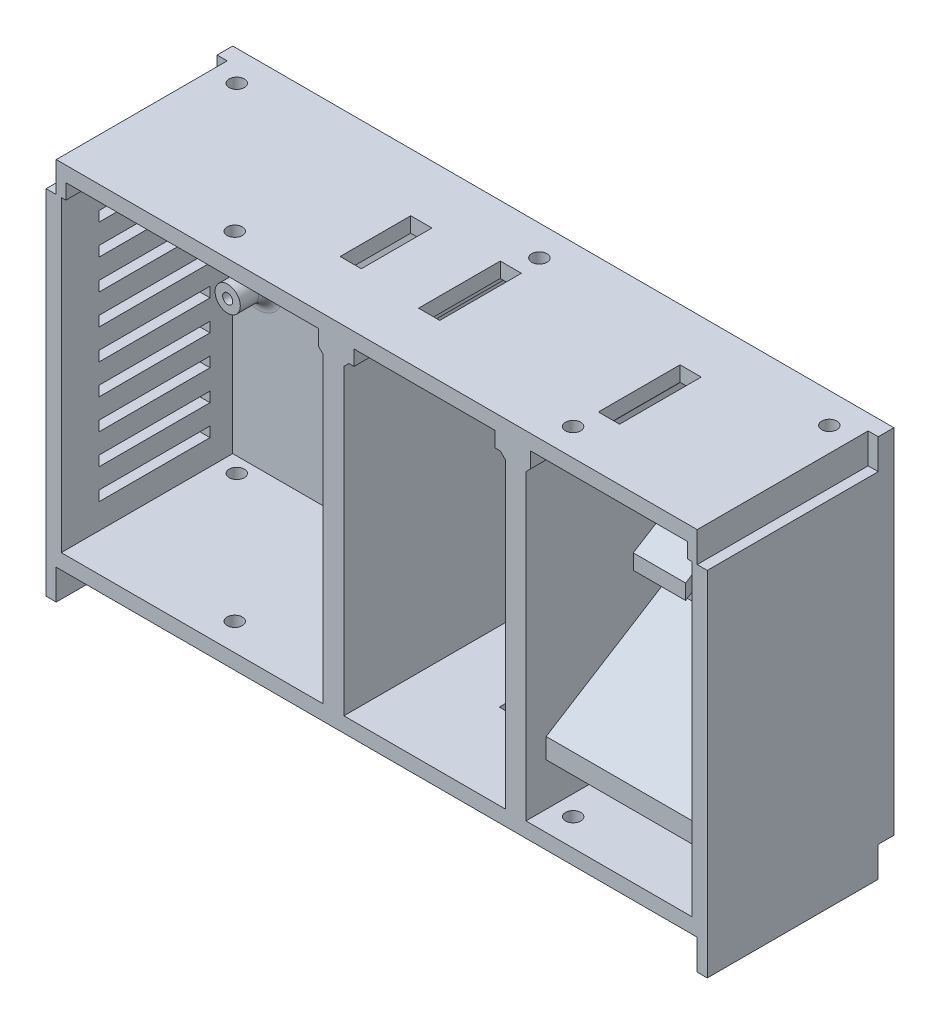
SolidWorks part; units mm, degrees
material "ABS"
ref_plane "Alzado" through (0, 0, 0) normal (0, 0, 1) x (1, 0, 0)
ref_plane "Planta" through (0, 0, 0) normal (0, 1, 0) x (1, 0, 0)
ref_plane "Vista lateral" through (0, 0, 0) normal (1, 0, 0) x (0, 0, -1)
sketch "Croquis1" plane through (0, 0, 0) normal (0, 0, 1) x (1, 0, 0)
  line L0 (0, 0) -> (2, 0)
  line L1 (2, 0) -> (2, 6)
  line L2 (55, 0) -> (55, 6)
  line L3 (55, 6) -> (2, 6)
  line L4 (56, 0) -> (56, 6)
  line L5 (56, 6) -> (58, 6)
  line L6 (58, 6) -> (58, 0)
  line L7 (58, 0) -> (59, 0)
  line L8 (59, 0) -> (59, 6)
  line L9 (91.1, 0) -> (91.1, 6)
  line L10 (59, 6) -> (91.1, 6)
  line L11 (92.1, 0) -> (92.1, 6)
  line L12 (92.1, 6) -> (94.1, 6)
  line L13 (94.1, 6) -> (94.1, 0)
  line L14 (95.1, 0) -> (95.1, 6)
  line L15 (129.1, 0) -> (129.1, 6)
  line L16 (129.1, 6) -> (95.1, 6)
  line L17 (0, 0) -> (0, -64)
  line L18 (0, -64) -> (131.1, -64)
  line L19 (131.1, -64) -> (131.1, 0)
  line L20 (55, 0) -> (56, 0)
  line L21 (58, 0) -> (59, 0)
  line L22 (129.1, 0) -> (131.1, 0)
  line L23 (94.1, 0) -> (95.1, 0)
  line L24 (91.1, 0) -> (92.1, 0)
  line L25 (2, 0) -> (129.1, 0)
  line L26 (55, 6) -> (56, 6)
  line L27 (58, 6) -> (59, 6)
  line L28 (91.1, 6) -> (92.1, 6)
  line L29 (94.1, 6) -> (95.1, 6)
  point P3 (2, 0)
  point P4 (129.1, 0)
  point P5 (55, 0)
  point P10 (56, 0)
  point P11 (58, 0)
  point P12 (59, 0)
  point P15 (91.1, 0)
  point P22 (92.1, 0)
  point P23 (94.1, 0)
  point P24 (95.1, 0)
  dimension "D1" = 131.1
  dimension "D2" = 2
  dimension "D3" = 2
  dimension "D4" = 55
  dimension "D5" = 6
  dimension "D6" = 1
  dimension "D7" = 2
  dimension "D8" = 1
  dimension "D9" = 32.1
  dimension "D10" = 1
  dimension "D11" = 2
  dimension "D12" = 1
  dimension "D13" = 64
extrude "Saliente-Extruir1" add sketch "Croquis1" along normal blind 34 contours L8 L25 L9 L10 | L1 L25 L2 L3 | L14 L25 L15 L16 | L11 L25 L13 L12 | L4 L25 L6 L5 | L26 L2 L20 L4 | L27 L6 L7 L8 | L29 L13 L23 L14 | L28 L9 L24 L11 region at (28.5, 3, 0) region at (55.5, 3, 0) region at (57, 3, 0) region at (58.5, 3, 0) region at (112.1, 3, 0) region at (75.05, 3, 0) region at (94.6, 3, 0) region at (91.6, 3, 0) region at (93.1, 3, 0)
sketch "Croquis2" plane through (0, 0, 0) normal (0, 0, 1) x (1, 0, 0)
  line L1 (2, -64) -> (129.1, -64)
  line L3 (129.1, 0) -> (2, 0)
  line L5 (129.1, 0) -> (131.1, 0)
  line L7 (129.1, -64) -> (131.1, -64)
  line L8 (131.1, 0) -> (131.1, -64)
  line L9 (2, -64) -> (0, -64)
  line L11 (2, 0) -> (0, 0)
  line L12 (0, -64) -> (0, 0)
  dimension "D1" = 64
  dimension "D2" = 2
  dimension "D3" = 2
extrude "Saliente-Extruir2" add sketch "Croquis2" along normal blind 3
sketch "Croquis3" plane through (0, 0, 3) normal (0, 0, 1) x (1, 0, 0)
  line L0 (0, -64) -> (131.1, -64) construction
  line L1 (131.1, 0) -> (128.1, 0)
  line L2 (131.1, 0) -> (131.1, -64)
  line L3 (131.1, -64) -> (128.1, -64)
  line L4 (128.1, 0) -> (128.1, -61)
  line L6 (0, 0) -> (3, 0)
  line L7 (0, 0) -> (0, -64)
  line L8 (0, -64) -> (3, -64)
  line L9 (3, 0) -> (3, -61)
  line L10 (3, -64) -> (128.1, -64)
  line L12 (3, -61) -> (128.1, -61)
  dimension "D1" = 3
  dimension "D2" = 3
  dimension "D3" = 3
extrude "Saliente-Extruir3" add sketch "Croquis3" along normal up to vertex (31 mm away) up to point (129.1, 0, 34)
sketch "Croquis4" plane through (0, 0, 0) normal (0, 0, -1) x (-1, 0, 0)
  line L25 (-2, 6) -> (-129.1, 6)
  line L34 (-129.1, 6) -> (-129.1, 0)
  line L35 (-129.1, 0) -> (-131.1, 0)
  line L36 (-131.1, 0) -> (-131.1, -64)
  line L37 (-131.1, -64) -> (0, -64)
  line L38 (0, -64) -> (0, 0)
  line L39 (0, 0) -> (-2, 0)
  line L40 (-2, 0) -> (-2, 6)
  line L49 (-2, 6) -> (-129.1, 6)
  line L58 (-129.1, 6) -> (-129.1, 0)
  line L59 (-129.1, 0) -> (-131.1, 0)
  line L60 (-131.1, 0) -> (-131.1, -64)
  line L61 (-131.1, -64) -> (0, -64)
  line L62 (0, -64) -> (0, 0)
  line L63 (0, 0) -> (-2, 0)
  line L64 (-2, 0) -> (-2, 6)
  dimension "D1" = 0
extrude "Saliente-Extruir4" add sketch "Croquis4" along normal blind 3
sketch "Croquis5" plane through (0, 0, 3) normal (0, 0, 1) x (1, 0, 0)
  line L1 (128.1, -61) -> (3, -61) construction
  line L4 (0, -64) -> (0, 0) construction
  line L23 (54.95, 0.05) -> (59.05, 0.05)
  line L26 (128.1, 0) -> (3, 0) construction
  line L27 (54.95, 0.05) -> (54.95, -61)
  line L28 (59.05, 0.05) -> (59.05, -61)
  line L29 (91.05, 0.05) -> (95.15, 0.05)
  line L32 (196.65, 0) -> (-65.55, 0) construction
  line L33 (91.05, 0.05) -> (91.05, -61)
  line L34 (128.1, -61) -> (3, -61) construction
  line L35 (91.05, -61) -> (95.15, -61)
  line L36 (95.15, -61) -> (95.15, 0.05)
  line M6 (128.1, 0) -> (3, 0)
  line M8 (128.1, 0) -> (3, 0)
  line M10 (128.1, 0) -> (3, 0)
  line M12 (128.1, 0) -> (3, 0)
  line M14 (128.1, 0) -> (3, 0)
  line M16 (3, -61) -> (128.1, -61)
  dimension "D1" = 54.95
  dimension "D2" = 32
  dimension "D3" = 4.1
  dimension "D4" = 0.05
  dimension "D6" = 0.05
extrude "Saliente-Extruir10" add sketch "Croquis5" along normal up to vertex (31 mm away) contours L28 L27 M10 M12 M14 M16 | L36 L33 M16 M6 M8 M10 region at (57, -30.5, 3) region at (93.1, -30.5, 3) up to point (3, 0, 34)
sketch "Croquis6" plane through (0, 0, 0) normal (0, -1, 0) x (1, 0, 0)
  line L0 (0, 34) -> (0, -3) construction
  line L1 (0, 15.5) -> (131.1, 15.5) construction
  line L2 (131.1, 34) -> (131.1, -3) construction
  line L3 (51, 8.5) -> (51, 22.5)
  line L4 (51, 22.5) -> (46.8, 22.5)
  line L5 (46.8, 22.5) -> (46.8, 8.5)
  line L6 (46.8, 8.5) -> (51, 8.5)
  line L7 (99.1, 7.4) -> (99.1, 23.6)
  line L8 (99.1, 23.6) -> (103.3, 23.6)
  line L9 (103.3, 23.6) -> (103.3, 7.4)
  line L10 (103.3, 7.4) -> (99.1, 7.4)
  line L11 (63.45, 7.4) -> (63.45, 23.6)
  line L12 (63.45, 23.6) -> (67.65, 23.6)
  line L13 (67.65, 23.6) -> (67.65, 7.4)
  line L14 (67.65, 7.4) -> (63.45, 7.4)
  point P6 (99.1, 15.5)
  point P9 (51, 15.5)
  point P15 (99.1, 15.5)
  point P17 (63.45, 15.5)
  point P21 (63.45, 15.5)
  dimension "D1" = 51
  dimension "D2" = 4.2
  dimension "D3" = 14
  dimension "D4" = 32
  dimension "D5" = 16.2
  dimension "D6" = 4.2
  dimension "D7" = 12.45
extrude "Cortar-Extruir1" cut sketch "Croquis6" against normal up to next
sketch "Croquis7" plane through (0, 0, 34) normal (0, 0, 1) x (1, 0, 0)
  line L0 (3, 0) -> (54.95, 0) construction
  line L1 (28.975, 0) -> (28.975, 3)
  line L2 (3.925, 3) -> (54.025, 3)
  line L3 (54.025, 3) -> (54.025, 0)
  line L4 (3.925, 0) -> (54.025, 0)
  line L5 (3.925, 3) -> (3.925, 0)
  line L6 (75.05, 0) -> (75.05, 3)
  line L7 (59.05, 0) -> (91.05, 0) construction
  line L8 (75.05, 3) -> (89.05, 3)
  line L9 (89.05, 3) -> (89.05, 0)
  line L10 (89.05, 0) -> (75.05, 0)
  line L11 (75.05, 3) -> (61.05, 3)
  line L12 (61.05, 3) -> (61.05, 0)
  line L13 (61.05, 0) -> (75.05, 0)
  line L14 (61.05, 3) -> (75.05, 3)
  line L15 (111.625, 0) -> (111.625, 3)
  line L16 (95.15, 0) -> (128.1, 0) construction
  line L17 (111.625, 3) -> (127.225, 3)
  line L18 (127.225, 3) -> (127.225, 0)
  line L19 (127.225, 0) -> (111.625, 0)
  line L20 (111.625, 0) -> (96.025, 0)
  line L21 (96.025, 0) -> (96.025, 3)
  line L22 (96.025, 3) -> (111.625, 3)
  line M5 (59.05, 0) -> (91.05, 0)
  line M10 (95.15, 0) -> (128.1, 0)
  line M37 (3, 0) -> (54.95, 0)
  dimension "D1" = 25.05
  dimension "D2" = 3
  dimension "D3" = 14
  dimension "D4" = 15.6
extrude "Cortar-Extruir2" cut sketch "Croquis7" against normal up to vertex (31 mm away) contours L3 L2 L1 M37 | L2 L5 L1 M37 | L11 L12 L6 M5 | L9 L8 L6 M5 | L22 L21 L15 M10 | L18 L17 L15 M10 region at (16.45, 1.5, 34) region at (41.5, 1.5, 34) region at (68.05, 1.5, 34) region at (82.05, 1.5, 34) region at (103.825, 1.5, 34) region at (119.425, 1.5, 34) up to point (54.95, 0, 3)
sketch "Croquis22" plane through (0, 0, 3) normal (0, 0, 1) x (1, 0, 0)
  line L0 (95.15, 0) -> (95.15, -61) construction
  line L1 (95.15, -61) -> (128.1, -61) construction
  line L2 (128.1, -61) -> (128.1, 0) construction
  line L3 (128.1, 0) -> (127.225, 0) construction
  line L4 (127.225, 0) -> (127.225, 3) construction
  line L5 (127.225, 3) -> (96.025, 3) construction
  line L6 (96.025, 3) -> (96.025, 0) construction
  line L7 (96.025, 0) -> (95.15, 0) construction
  line L8 (91.05, -61) -> (91.05, 0) construction
  line L9 (91.05, 0) -> (89.05, 0) construction
  line L10 (89.05, 0) -> (89.05, 3) construction
  line L11 (89.05, 3) -> (61.05, 3) construction
  line L12 (61.05, 3) -> (61.05, 0) construction
  line L13 (61.05, 0) -> (59.05, 0) construction
  line L14 (59.05, 0) -> (59.05, -61) construction
  line L15 (59.05, -61) -> (91.05, -61) construction
  line L16 (54.95, -61) -> (54.95, 0) construction
  line L17 (54.95, 0) -> (54.025, 0) construction
  line L18 (54.025, 0) -> (54.025, 3) construction
  line L19 (54.025, 3) -> (3.925, 3) construction
  line L20 (3.925, 3) -> (3.925, 0) construction
  line L21 (3.925, 0) -> (3, 0) construction
  line L22 (3, 0) -> (3, -61) construction
  line L23 (3, -61) -> (54.95, -61) construction
  line L24 (95.15, 0) -> (95.15, -61)
  line L25 (95.15, -61) -> (128.1, -61)
  line L26 (128.1, -61) -> (128.1, 0)
  line L27 (128.1, 0) -> (127.225, 0)
  line L28 (127.225, 0) -> (127.225, 3)
  line L29 (127.225, 3) -> (96.025, 3)
  line L30 (96.025, 3) -> (96.025, 0)
  line L31 (96.025, 0) -> (95.15, 0)
  line L32 (91.05, -61) -> (91.05, 0)
  line L33 (91.05, 0) -> (89.05, 0)
  line L34 (89.05, 0) -> (89.05, 3)
  line L35 (89.05, 3) -> (61.05, 3)
  line L36 (61.05, 3) -> (61.05, 0)
  line L37 (61.05, 0) -> (59.05, 0)
  line L38 (59.05, 0) -> (59.05, -61)
  line L39 (59.05, -61) -> (91.05, -61)
  line L40 (54.95, -61) -> (54.95, 0)
  line L41 (54.95, 0) -> (54.025, 0)
  line L42 (54.025, 0) -> (54.025, 3)
  line L43 (54.025, 3) -> (3.925, 3)
  line L44 (3.925, 3) -> (3.925, 0)
  line L45 (3.925, 0) -> (3, 0)
  line L46 (3, 0) -> (3, -61)
  line L47 (3, -61) -> (54.95, -61)
extrude "Cortar-Extruir8" cut sketch "Croquis22" against normal blind 3 contours L40 L41 L42 L43 L44 L45 L46 L47 | L32 L33 L34 L35 L36 L37 L38 L39 | L24 L25 L26 L27 L28 L29 L30 L31
sketch "Croquis24" plane through (2, 0, 0) normal (-1, 0, 0) x (0, 0, 1)
  line L0 (34, 0) -> (-3, 0) construction
  line L5 (0.1, 0) -> (-4.3164, 0)
  line L6 (0.1, 0) -> (0.1, 6.5451)
  line L7 (0.1, 6.5451) -> (-4.3164, 6.5451)
  line L8 (-4.3164, 0) -> (-4.3164, 6.5451)
  line L9 (0, 0) -> (0, 8.0802) construction
  dimension "D1" = 0.1
extrude "Cortar-Extruir11" cut sketch "Croquis24" against normal through all contours L6 L5 L8 L7
sketch "Croquis26" plane through (0, 0, 0) normal (0, 0, 1) x (1, 0, 0)
  line L0 (4, -60) -> (54.1, -60)
  line L1 (4, -60) -> (4, -4.1)
  line L2 (4, -4.1) -> (54.1, -4.1)
  line L3 (54.1, -60) -> (54.1, -4.1)
  line L4 (4, -60) -> (54.1, -4.1) construction
  line L5 (4, -4.1) -> (54.1, -60) construction
  line L6 (36.1, -45) -> (46.1, -45)
  line L7 (36.1, -45) -> (36.1, -39)
  line L8 (36.1, -39) -> (46.1, -39)
  line L9 (46.1, -45) -> (46.1, -39)
  line L10 (3, -61) -> (54.95, -61) construction
  line L11 (3, 0) -> (3, -61) construction
  line L12 (54.95, -61) -> (54.95, 0) construction
  circle A0 centre (24, -8.1) radius 1
  circle A1 centre (8, -28.9) radius 1
  circle A2 centre (24, -8.1) radius 2.5
  circle A3 centre (8, -28.9) radius 2.5
  point P0 (29.05, -32.05)
  point P5 (24, -8.1)
  point P8 (8, -28.9)
  dimension "D6" = 2
  dimension "D7" = 5
  dimension "D1" = 1
  dimension "D2" = 55.9
  dimension "D3" = 1
  dimension "D4" = 4
  dimension "D5" = 24.8
  dimension "D8" = 4
  dimension "D9" = 20
  dimension "D10" = 8
  dimension "D11" = 15
  dimension "D12" = 6
  dimension "D13" = 10
  dimension "D14" = 0.85
extrude "Saliente-Extruir16" add sketch "Croquis26" along normal blind 6 contours L6 L9 L8 L7 | A2 A0 | A3 A1 region at (41.1, -42, 0) region at (21.5707, -8.1, 0) region at (5.5707, -28.9, 0)
fillet "Redondeo1" radius 2.4 3 edges at (10.5, -28.9, 0) (26.5, -8.1, 0) (46.1, -42, 0)
chamfer "Chaflán1" distance 1 angle 45 4 edges at (54.95, 0, 17.05) (95.15, 0, 17.05) (91.05, 0, 17.05) (59.05, 0, 17.05)
sketch "Croquis10" plane through (0, 0, 0) normal (-1, 0, 0) x (0, 0, 1)
  line L0 (15.5, -64) -> (15.5, 6) construction
  line L1 (34, -64) -> (-3, -64) construction
  line L3 (4.5, -50) -> (4.5, -48)
  line L4 (4.5, -56) -> (26.5, -56)
  line L5 (4.5, -56) -> (4.5, -54)
  line L6 (4.5, -54) -> (26.5, -54)
  line L7 (26.5, -56) -> (26.5, -54)
  line L8 (4.5, -56) -> (26.5, -54) construction
  line L9 (4.5, -54) -> (26.5, -56) construction
  line L10 (4.5, -50) -> (26.5, -50)
  line L11 (26.5, -50) -> (26.5, -48)
  line L12 (4.5, -48) -> (26.5, -48)
  line L13 (4.5, -44) -> (4.5, -42)
  line L14 (4.5, -44) -> (26.5, -44)
  line L15 (26.5, -44) -> (26.5, -42)
  line L16 (4.5, -42) -> (26.5, -42)
  line L17 (4.5, -38) -> (4.5, -36)
  line L18 (4.5, -38) -> (26.5, -38)
  line L19 (26.5, -38) -> (26.5, -36)
  line L20 (4.5, -36) -> (26.5, -36)
  line L21 (4.5, -32) -> (4.5, -30)
  line L22 (4.5, -32) -> (26.5, -32)
  line L23 (26.5, -32) -> (26.5, -30)
  line L24 (4.5, -30) -> (26.5, -30)
  line L25 (4.5, -26) -> (4.5, -24)
  line L26 (4.5, -26) -> (26.5, -26)
  line L27 (26.5, -26) -> (26.5, -24)
  line L28 (4.5, -24) -> (26.5, -24)
  line L29 (4.5, -20) -> (4.5, -18)
  line L30 (4.5, -20) -> (26.5, -20)
  line L31 (26.5, -20) -> (26.5, -18)
  line L32 (4.5, -18) -> (26.5, -18)
  line L33 (4.5, -14) -> (4.5, -12)
  line L34 (4.5, -14) -> (26.5, -14)
  line L35 (26.5, -14) -> (26.5, -12)
  line L36 (4.5, -12) -> (26.5, -12)
  line L37 (4.5, -8) -> (4.5, -6)
  line L38 (4.5, -8) -> (26.5, -8)
  line L39 (26.5, -8) -> (26.5, -6)
  line L40 (4.5, -6) -> (26.5, -6)
  point P6 (15.5, -55)
  dimension "D1" = 22
  dimension "D2" = 2
  dimension "D3" = 8
  dimension "D4" = 9
extrude "Cortar-Extruir3" cut sketch "Croquis10" against normal up to vertex (3 mm away) contours L4 L7 L6 L5 | L12 L3 L10 L11 | L16 L13 L14 L15 | L20 L17 L18 L19 | L24 L21 L22 L23 | L28 L25 L26 L27 | L32 L29 L30 L31 | L36 L33 L34 L35 | L40 L37 L38 L39 region at (0, -49, 15.5) region at (0, -55, 15.5) region at (0, -43, 15.5) region at (0, -37, 15.5) region at (0, -31, 15.5) region at (0, -25, 15.5) region at (0, -19, 15.5) region at (0, -13, 15.5) region at (0, -7, 15.5) up to point (3, -61, 34)
sketch "Croquis12" plane through (95.15, 0, 0) normal (1, 0, 0) x (0, 0, -1)
  line L0 (0, -29.7544) -> (-34, -51)
  line L1 (0, 0) -> (0, -61) construction
  line L2 (-34, -61) -> (-34, -1) construction
  line L4 (-34, -51) -> (-34, -55)
  line L5 (-34, -55) -> (0, -33.7544)
  line L6 (0, -29.7544) -> (0, -33.7544)
  dimension "D1" = 4
  dimension "D2" = 58
  dimension "D3" = 6
extrude "Saliente-Extruir12" add sketch "Croquis12" along normal up to surface (32.95 mm away) up to face at (128.1, -24.4, 13.62)
sketch "Croquis13" plane through (95.15, 0, 0) normal (1, 0, 0) x (0, 0, -1)
  line L0 (0, -29.7544) -> (0, -20.6544) construction
  line L2 (0, -20.6544) -> (-12.7207, -28.6032)
  line L4 (0, -29.7544) -> (-34, -51) construction
  line L6 (-12.7207, -25.6032) -> (0, -17.6544)
  line L7 (0, -17.6544) -> (0, -20.6544)
  line L8 (-12.7207, -28.6032) -> (-12.7207, -25.6032)
  line L9 (-34, -51) -> (-8.7351, -35.2127) construction
  line L10 (0, -29.7544) -> (-34, -51) construction
  line L11 (-6.7844, -33.9938) -> (-6.7844, -24.8938)
  line L12 (-6.7844, -33.9938) -> (0, -29.7544)
  line L13 (0, 0) -> (0, -29.7544) construction
  line M8 (-34, -51) -> (0, -29.7544)
  line M18 (0, -29.7544) -> (0, 0)
  dimension "D1" = 9.1
  dimension "D2" = 3
  dimension "D3" = 15
  dimension "D4" = 8
extrude "Saliente-Extruir17" add sketch "Croquis13" along normal up to surface (32.95 mm away) contours L11 L2 M8 M18 | L8 L2 L6 M18 region at (95.15, -27.3241, 3.3922) region at (95.15, -23.1288, 6.3604) up to face at (128.1, -52.6886, 17)
ref_plane "Plano1" through (0, -17.6544, 0) normal (0, -1, 0) x (-1, 0, 0)
sketch "Croquis38" plane through (0, -17.6544, 0) normal (0, -1, 0) x (-1, 0, 0)
  line L0 (-111.625, 0) -> (-111.625, -34.0311) construction
  line L1 (-128.1, 0) -> (-95.15, 0) construction
  line L2 (-111.625, 0) -> (-117.725, 0)
  line L3 (-117.725, 0) -> (-117.725, -26)
  line L4 (-117.725, -26) -> (-105.525, -26)
  line L5 (-111.625, 0) -> (-105.525, 0)
  line L6 (-105.525, 0) -> (-105.525, -26)
  dimension "D1" = 6.1
  dimension "D2" = 6.1
  dimension "D3" = 26
  dimension "D4" = 26
extrude "Cortar-Extruir12" cut sketch "Croquis38" along normal up to vertex (16.3394 mm away) contours L0 L2 L3 L4 | L5 L0 L4 L6 region at (108.575, -17.6544, 13) region at (114.675, -17.6544, 13) up to point (128.1, -33.9938, 6.7844)
sketch "Croquis40" plane through (0, 3, 0) normal (0, -1, 0) x (1, 0, 0)
  line L0 (0, 34) -> (0, -3) construction
  line L1 (3.925, 34) -> (54.025, 34) construction
  line L2 (131.1, 34) -> (131.1, -3) construction
  line L3 (0, -3) -> (131.1, -3) construction
  circle A0 centre (32, 28.6) radius 1.5
  circle A1 centre (99.1, 28.6) radius 1.5
  circle A2 centre (6.8, 3) radius 1.5
  circle A3 centre (124.3, 3) radius 1.5
  circle A4 centre (66.8, 3) radius 1.5
  dimension "D3" = 3
  dimension "D1" = 32
  dimension "D2" = 5.4
  dimension "D4" = 32
  dimension "D5" = 6.8
  dimension "D6" = 6
  dimension "D7" = 6.8
  dimension "D8" = 60
extrude "Cortar-Extruir13" cut sketch "Croquis40" against normal up to next
sketch "Croquis48" plane through (0, 0, 0) normal (-1, 0, 0) x (0, 0, 1)
  line L1 (-3, 0) -> (0.1, 0)
  line L2 (-3, 0) -> (-3, 6)
  line L3 (-3, 6) -> (0.1, 6)
  line L4 (0.1, 0) -> (0.1, 6)
extrude "Saliente-Extruir20" add sketch "Croquis48" against normal up to vertex (131.1 mm away) up to point (131.1, 0, -3)
sketch "Croquis49" plane through (0, 0, 34) normal (0, 0, 1) x (1, 0, 0)
  line L0 (2, 0) -> (2, -64) construction
  line L1 (0, -64) -> (131.1, -64) construction
  line L2 (129.1, 0) -> (129.1, -64) construction
  line L4 (2, -64) -> (0, -64)
  line L5 (0, -64) -> (0, -70)
  line L6 (0, -70) -> (2, -70)
  line L7 (2, -70) -> (2, -64)
  line L8 (129.1, -64) -> (131.1, -64)
  line L9 (131.1, -64) -> (131.1, -70)
  line L10 (131.1, -70) -> (129.1, -70)
  line L11 (129.1, -70) -> (129.1, -64)
  line L12 (65.55, -64) -> (68.55, -64)
  line L16 (62.55, -64) -> (65.55, -64)
  dimension "D1" = 6
  dimension "D2" = 3
extrude "Saliente-Extruir21" add sketch "Croquis49" against normal up to vertex (33.9 mm away) contours L6 L7 L4 L5 | L16 | L12 | L11 L10 L9 L8 region at (1, -67, 34) region at (130.1, -67, 34) up to point (2, 0, 0.1)
sketch "Croquis50" plane through (0, -64, 0) normal (0, -1, 0) x (1, 0, 0)
  circle A0 centre (124.3, 3) radius 1.5 construction
  circle A1 centre (99.1, 28.6) radius 1.5 construction
  circle A3 centre (6.8, 3) radius 1.5 construction
  circle A4 centre (32, 28.6) radius 1.5 construction
  circle A5 centre (124.3, 3) radius 1.5
  circle A6 centre (99.1, 28.6) radius 1.5
  circle A8 centre (6.8, 3) radius 1.5
  circle A9 centre (32, 28.6) radius 1.5
extrude "Cortar-Extruir14" cut sketch "Croquis50" against normal up to surface (3 mm away) up to face at (28.975, -61, 17)
sketch "Croquis51" plane through (0, 0, 0) normal (-1, 0, 0) x (0, 0, 1)
  line L0 (0.1, -64) -> (-3, -64) construction
  line L1 (-3, 6) -> (-2.9, 6)
  line L2 (-3, 6) -> (-3, -64)
  line L3 (-3, -64) -> (-2.9, -64)
  line L4 (-2.9, 6) -> (-2.9, -64)
  dimension "D1" = 0.1
extrude "Cortar-Extruir15" cut sketch "Croquis51" against normal through all
sketch "Croquis52" plane through (0, -64, 0) normal (0, -1, 0) x (1, 0, 0)
  line L1 (72.95, 17.1) -> (78.95, 17.1)
  line L2 (72.95, 17.1) -> (72.95, 9.1)
  line L3 (72.95, 9.1) -> (78.95, 9.1)
  line L4 (78.95, 17.1) -> (78.95, 9.1)
  line L5 (131.1, -2.9) -> (0, -2.9) construction
  line L6 (0, 0.1) -> (0, 34) construction
  dimension "D2" = 12
  dimension "D3" = 8
  dimension "D4" = 6
  dimension "D5" = 72.95
extrude "Cortar-Extruir16" cut sketch "Croquis52" against normal up to vertex (3 mm away) up to point (59.05, -61, 34)
sketch "Croquis53" plane through (0, 0, 34) normal (0, 0, 1) x (1, 0, 0)
  line L0 (128.1, 0) -> (128.1, -51) construction
  line L1 (95.15, -51) -> (128.1, -51)
  line L2 (95.15, -51) -> (95.15, -55)
  line L3 (95.15, -55) -> (128.1, -55)
  line L4 (128.1, -51) -> (128.1, -55)
  line L5 (95.15, -51) -> (128.1, -51)
  line L6 (95.15, -51) -> (95.15, -48.3278)
  line L7 (95.15, -48.3278) -> (128.1, -48.3278)
  line L8 (128.1, -51) -> (128.1, -48.3278)
extrude "Cortar-Extruir17" cut sketch "Croquis53" against normal blind 4 contours L4 L1 L2 L3 | L1 L8 L7 L6 region at (111.625, -49.6639, 34) region at (111.625, -53, 34)
sketch "Croquis54" plane through (0, 0, -2.9) normal (0, 0, -1) x (-1, 0, 0)
  line L1 (-131.1, 6) -> (0, 6)
  line L2 (-131.1, 6) -> (-131.1, -64)
  line L3 (-131.1, -64) -> (0, -64)
  line L4 (0, 6) -> (0, -64)
extrude "Saliente-Extruir22" add sketch "Croquis54" along normal blind 0.1
